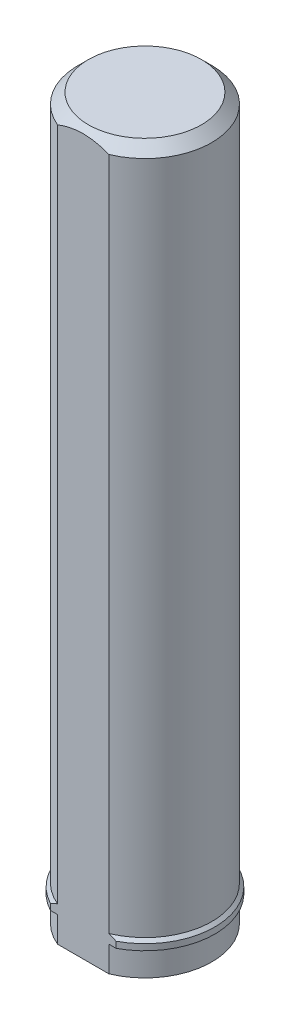
SolidWorks part; units mm, degrees
ref_plane "Top Plane" through (0, 0, 0) normal (0, 0, 1) x (1, 0, 0)
ref_plane "Right Plane" through (0, 0, 0) normal (0, 1, 0) x (1, 0, 0)
ref_plane "Front Plane" through (0, 0, 0) normal (1, 0, 0) x (0, 0, -1)
sketch "Sketch1" plane through (0, 0, 0) normal (0, 1, 0) x (1, 0, 0)
  line L0 (-1.25, -3) -> (1.25, -3)
  arc A0 (1.25, -3) -> (-1.25, -3) centre (0, 0) ccw
  dimension "D1" = 6.5
  dimension "D2" = 2.5
extrude "Boss-Extrude1" add sketch "Sketch1" along normal mid plane 35
sketch "Sketch2" plane through (0, -17.5, 0) normal (0, -1, 0) x (1, 0, 0)
  line L0 (-1.25, 3) -> (-1.6, 3)
  line L1 (1.25, 3) -> (1.6, 3)
  arc A1 (-1.25, 3) -> (1.25, 3) centre (0, 0) ccw construction
  arc A2 (-1.3077, 3.1385) -> (1.3077, 3.1385) centre (0, 0) ccw
  arc A3 (-1.6, 3) -> (1.6, 3) centre (0, 0) ccw
  arc A4 (-1.25, 3) -> (1.25, 3) centre (0, 0) ccw
  dimension "D1" = 0.15
extrude "Boss-Extrude2" add sketch "Sketch2" against normal blind 0.5 from offset 1.25 offset against normal yes
chamfer "Chamfer1" distance 0.2 angle 45 1 edges at (0, -15.75, -3.4)
chamfer "Chamfer2" distance 0.5 angle 45 1 edges at (0, 17.5, -3.25)
